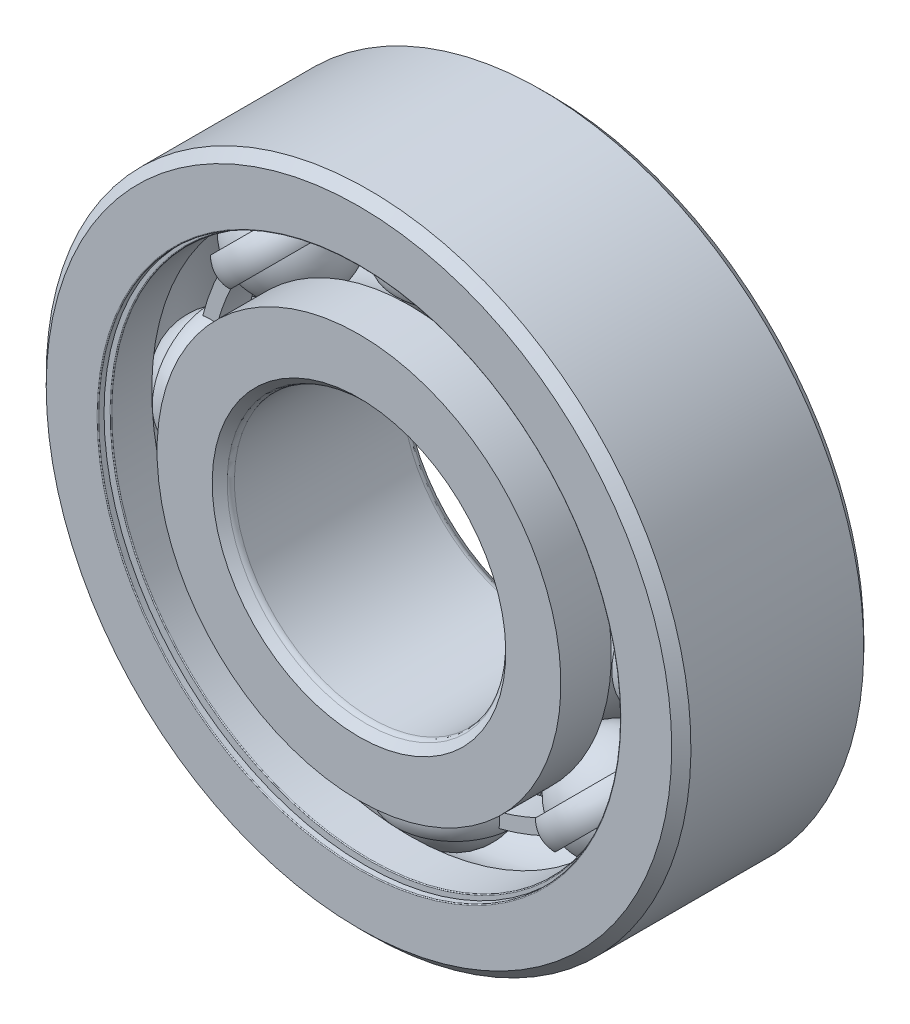
SolidWorks part; units mm, degrees
ref_plane "Front Plane" through (0, 0, 0) normal (0, 0, 1) x (1, 0, 0)
ref_plane "Top Plane" through (0, 0, 0) normal (0, 1, 0) x (1, 0, 0)
ref_plane "Right Plane" through (0, 0, 0) normal (1, 0, 0) x (0, 0, -1)
sketch "Sketch1" plane through (0, 0, 0) normal (0, 0, 1) x (1, 0, 0)
  line L0 (-23.5, 0) -> (23.5, 0) construction
  line L1 (-10, 0) -> (10, 0) construction
  circle A0 centre (0, 0) radius 10 construction
  circle A1 centre (0, 0) radius 23.5 construction
  point P3 (0, 0)
  point P6 (0, 0)
  point P7 (0, -10)
  point P11 (0, -23.5)
  point P12 (0, 10)
  point P13 (0, 23.5)
  dimension "OD" = 47
  dimension "ID" = 20
sketch "Sketch2" plane through (0, 0, 0) normal (1, 0, 0) x (0, 0, -1)
  line L0 (-7, 23.5) -> (7, 23.5) construction
  line L1 (0, 23.5) -> (0, -23.5) construction
  line L2 (6.3, 23.5) -> (-6.3, 23.5)
  line L3 (-6.3, 23.5) -> (-7, 22.8)
  line L4 (-7, 22.8) -> (-7, 18.7808)
  line L5 (-7, 18.7808) -> (-3.325, 18.7808)
  line L6 (7, 18.7808) -> (3.325, 18.7808)
  line L7 (7, 22.8) -> (7, 18.7808)
  line L8 (6.3, 23.5) -> (7, 22.8)
  line L9 (0, 23.5) -> (0, 16.75) construction
  line L10 (0, 16.75) -> (0, 10) construction
  line L11 (0, 23.5) -> (0, -23.5) construction
  line L12 (-7, 0) -> (7, 0) construction
  line L13 (7, 10) -> (-7, 10) construction
  line L14 (0, 20.6461) -> (0, 12.8539) construction
  line L15 (-7, -10) -> (7, -10) construction
  line L16 (-7, -10) -> (-7, 10) construction
  line L17 (7, 23.5) -> (7, -23.5) construction
  arc A0 (-3.325, 18.7808) -> (3.325, 18.7808) centre (0, 16.75) cw
  circle A1 centre (0, 16.75) radius 3.8961 construction
  point P14 (0, 10)
  point P17 (0, 0)
  point P21 (0, 23.5)
  point P29 (0, 10)
  point P30 (0, -10)
  point P35 (0, 20.6461)
  dimension "Approx. Ball Dia." = 7.7922
  dimension "Width" = 14
  dimension "D1" = 45
  dimension "D2" = 0.7
  dimension "D3" = 6.65
  dimension "D4" = 2.0308
  dimension "For Shaft Diameter" = 20
  dimension "For Housing ID" = 47
sketch "Sketch3" plane through (0, 0, 0) normal (1, 0, 0) x (0, 0, -1)
  line L0 (6.3, 23.5) -> (7, 22.8) construction
  line L1 (7, 22.8) -> (7, 18.7808) construction
  line L2 (7, 18.7808) -> (3.325, 18.7808) construction
  line L3 (-7, 18.7808) -> (-3.325, 18.7808) construction
  line L4 (-7, 22.8) -> (-7, 18.7808) construction
  line L5 (-6.3, 23.5) -> (-7, 22.8) construction
  line L6 (6.3, 23.5) -> (-6.3, 23.5) construction
  line L7 (6.3, 23.5) -> (7, 22.8)
  line L8 (7, 22.8) -> (7, 18.7808)
  line L9 (7, 18.7808) -> (3.325, 18.7808)
  line L10 (-7, 18.7808) -> (-3.325, 18.7808)
  line L11 (-7, 22.8) -> (-7, 18.7808)
  line L12 (-6.3, 23.5) -> (-7, 22.8)
  line L13 (6.3, 23.5) -> (-6.3, 23.5)
  arc A0 (3.325, 18.7808) -> (-3.325, 18.7808) centre (0, 16.75) ccw construction
  arc A1 (3.325, 18.7808) -> (-3.325, 18.7808) centre (0, 16.75) ccw
revolve "Revolve1" add sketch "Sketch3" angle 360 about L12
sketch "Sketch8" plane through (0, 0, 0) normal (1, 0, 0) x (0, 0, -1)
  line L0 (-7, 18.7808) -> (-3.325, 18.7808) construction
  line L1 (-6.552, 18.7808) -> (-6.3, 18.7808)
  line L2 (-6.552, 18.7808) -> (-6.552, 20.3538) construction
  line L3 (-6.552, 20.3538) -> (-6.3, 20.3538)
  line L4 (-6.3, 18.7808) -> (-6.3, 20.3538)
  line L5 (7, 18.7808) -> (3.325, 18.7808) construction
  line L6 (6.3, 18.7808) -> (6.552, 18.7808)
  line L7 (6.3, 18.7808) -> (6.3, 20.3538)
  line L8 (6.3, 20.3538) -> (6.552, 20.3538)
  line L9 (6.552, 18.7808) -> (6.552, 20.3538) construction
  line L10 (-6.3, 20.3538) -> (6.3, 20.3538) construction
  line L11 (0, 23.5) -> (0, -23.5) construction
  line L12 (-6.552, 20.3538) -> (-6.552, 21.9269) construction
  line L13 (-6.552, 21.9269) -> (-6.552, 23.5) construction
  line L14 (-7, 23.5) -> (7, 23.5) construction
  line L15 (-6.552, 18.7808) -> (-7, 18.7808)
  line L16 (-7, 18.7808) -> (-7, 19.0328)
  line L17 (-7, 22.8) -> (-7, 18.7808) construction
  line L18 (-7, 19.0328) -> (-6.552, 19.0328)
  line L19 (-6.552, 19.0328) -> (-6.552, 20.3538)
  line L20 (6.552, 18.7808) -> (7, 18.7808)
  line L21 (7, 18.7808) -> (7, 19.0328)
  line L22 (7, 22.8) -> (7, 18.7808) construction
  line L23 (7, 19.0328) -> (6.552, 19.0328)
  line L24 (6.552, 19.0328) -> (6.552, 20.3538)
  point P12 (0, 20.3538)
  dimension "D1" = 12.6
  dimension "D2" = 0.252
revolve "Cut-Revolve1" cut sketch "Sketch8" angle 360 about L12
sketch "Sketch4" plane through (0, 0, 0) normal (1, 0, 0) x (0, 0, -1)
  line L0 (0, 23.5) -> (0, -23.5) construction
  line L1 (0, 23.5) -> (0, -23.5) construction
  line L2 (-6.3, 10) -> (-7, 10.7)
  line L3 (-7, 10.7) -> (-7, 14.7192)
  line L5 (-7, 14.7192) -> (-3.325, 14.7192)
  line L6 (-6.3, 10) -> (6.3, 10)
  line L8 (6.3, 10) -> (7, 10.7)
  line L10 (7, 10.7) -> (7, 14.7192)
  line L11 (7, 14.7192) -> (3.325, 14.7192)
  line L12 (-7, 22.8) -> (-7, 18.7808) construction
  line L13 (6.3, 23.5) -> (7, 22.8) construction
  line L15 (7, -22.8) -> (7, 22.8) construction
  line L16 (6.3, 23.5) -> (6.3, -23.5) construction
  arc A1 (3.325, 14.7192) -> (-3.325, 14.7192) centre (0, 16.75) cw
  circle A2 centre (0, 16.75) radius 3.8961 construction
  point P1 (0, 10)
revolve "Revolve2" add sketch "Sketch4" angle 360 about L12
sketch "Sketch5" plane through (0, 0, 0) normal (1, 0, 0) x (0, 0, -1)
  line L0 (-3.8961, 16.75) -> (3.8961, 16.75)
  arc A2 (-3.8961, 16.75) -> (3.8961, 16.75) centre (0, 16.75) cw
  arc A3 (3.325, 18.7808) -> (-3.325, 18.7808) centre (0, 16.75) ccw construction
revolve "Revolve3" add sketch "Sketch5" angle 360 about L0
sketch "Sketch6" plane through (0, 0, 0) normal (1, 0, 0) x (0, 0, -1)
  line L0 (-3.325, 18.7808) -> (-3.325, 17.7654) construction
  line L1 (-3.325, 17.7654) -> (-3.325, 16.75) construction
  line L2 (-3.325, 16.75) -> (-3.325, 15.7346) construction
  line L3 (-3.325, 15.7346) -> (-3.325, 14.7192) construction
  line L4 (-7, 17.7654) -> (-6.4602, 17.7654) construction
  line L5 (-3.325, 17.7654) -> (-3.325, 15.7346) construction
  line L7 (-6.4602, 17.7654) -> (-5.9205, 17.7654) construction
  line L8 (-5.9205, 17.7654) -> (-5.3807, 17.7654) construction
  line L10 (0, 23.5) -> (0, -23.5) construction
  line L11 (0, 23.5) -> (0, -23.5) construction
  line L12 (-7, 18.7808) -> (-7, 17.7654) construction
  line L13 (-4.3012, 17.7654) -> (-3.7615, 17.7654) construction
  line L14 (-7, 22.8) -> (-7, -22.8) construction
  line L15 (-7, 17.7654) -> (-7, 16.75) construction
  line L16 (-7, 16.75) -> (-7, 15.7346) construction
  line L17 (-7, 15.7346) -> (-7, 14.7192) construction
  line L18 (-5.3807, 17.7654) -> (-4.841, 17.7654) construction
  line L19 (-4.841, 17.7654) -> (-4.3012, 17.7654) construction
  line L20 (-3.7615, 17.7654) -> (-4.3012, 17.7654)
  line L21 (-7, 15.7346) -> (-6.4602, 15.7346) construction
  line L22 (-6.4602, 15.7346) -> (-5.9205, 15.7346) construction
  line L23 (-5.9205, 15.7346) -> (-5.3807, 15.7346) construction
  line L24 (-5.3807, 15.7346) -> (-4.841, 15.7346) construction
  line L25 (-4.841, 15.7346) -> (-4.3012, 15.7346) construction
  line L26 (-4.3012, 15.7346) -> (-3.7615, 15.7346) construction
  line L27 (-3.7615, 15.7346) -> (-4.3012, 15.7346)
  line L28 (-4.841, 17.7654) -> (-4.841, 15.7346) construction
  line L30 (-4.5711, 17.7654) -> (-4.5711, 15.7346) construction
  circle A0 centre (0, 16.75) radius 3.8961 construction
  arc A2 (-4.3012, 15.7346) -> (-4.3012, 17.7654) centre (-2.526, 16.75) cw
  arc A3 (-3.7615, 17.7654) -> (-3.7615, 15.7346) centre (0, 16.75) ccw
revolve "Revolve4" add sketch "Sketch6" angle 360 about L11
sketch "Sketch7" plane through (0, 0, 0) normal (0, 0, 1) x (1, 0, 0)
  line L0 (-3.8961, 16.75) -> (3.8961, 16.75) construction
  line L1 (0, 12.8539) -> (0, 20.6461) construction
  line L2 (0, 0) -> (6.7455, 15.3317) construction
  line L8 (0, 23.5) -> (0, -23.5) construction
  line L9 (12.3486, 11.317) -> (13.0971, 12.0031)
  line L10 (0, 23.5) -> (0, -23.5) construction
  line L11 (0, 17.7654) -> (0, 16.75)
  arc A1 (12.3486, 11.317) -> (0, 16.75) centre (0, 0) ccw
  arc A2 (13.0971, 12.0031) -> (0, 17.7654) centre (0, 0) ccw
  dimension "D1" = 47.496
  dimension "D2" = 7.7922
extrude "Boss-Extrude1" add sketch "Sketch7" along normal mid plane 2.3333
pattern_circular "CirPattern1" count 8 over 360 about axis through (0, 0, 7) along (0, 0, -1) of bodies 104 134
pattern_circular "CirPattern2" count 8 over 360 about axis through (0, 0, 7) along (0, 0, -1) of "Revolve4", "Boss-Extrude1" reverse direction yes
fillet "Fillet1" radius 0.063 4 edges at (0, -18.7808, -6.3) (0, -19.0328, -7) (0, -18.7808, 6.3) (0, -19.0328, 7)
fillet "Fillet2" radius 0.525 2 edges at (0, -10, -6.3) (0, -10, 6.3)
ref_plane "Plane1" through (6.7455, 15.3317, 0) normal (0.4027, 0.9153, 0) x (0.9153, -0.4027, 0)
sketch "Sketch9" plane through (6.7455, 15.3317, 0) normal (0.4027, 0.9153, 0) x (0.9153, -0.4027, 0)
  line L0 (-3.1792, -1.1667) -> (-3.1792, -3.5)
  line L1 (-3.1792, -3.5) -> (-1.379, -3.5)
  line L2 (-1.379, -3.5) -> (0, -2.3429)
  line L3 (0, -2.3429) -> (1.379, -3.5)
  line L4 (1.379, -3.5) -> (3.1792, -3.5)
  line L5 (3.1792, -3.5) -> (3.1792, -1.1667)
  line L6 (3.1792, -1.1667) -> (-3.1792, -1.1667)
  line L7 (0, -1.1667) -> (0, 0) construction
  line L8 (-3.1792, -1.1667) -> (-3.1792, 0) construction
  dimension "D1" = 2.3333
  dimension "D2" = 1.1667
  dimension "D3" = 40
extrude "Boss-Extrude2" [suppressed] add sketch "Sketch9" along normal blind 3.4091 draft 15 and the other way blind 3.4091 draft 10 separate body draft outward yes other way draft outward yes
fillet "Fillet3" [suppressed] radius 0.7
mirror "Mirror1" [suppressed] about plane through (0, 0, 0) normal (0, 0, 1) of bodies 149
pattern_circular "CirPattern3" [suppressed] count 8 over 360 about axis through (0, 0, 7) along (0, 0, -1) of bodies 158 149
ref_axis "Axis1" through (0, 0, -7.7) along (0, 0, 1)
equation "\"D2@Sketch2\" = \"Width@Sketch2\" * .05"
equation "\"D3@Sketch2\"=\"Width@Sketch2\" * .475"
equation "\"D4@Sketch2\" =  (  (  ( \"OD@Sketch1\" - \"Width@Sketch2\" )  / 2 )  / 3.25 )  / 2.5"
equation "\"D1@Boss-Extrude1\" = \"Width@Sketch2\" / 6"
equation "\"D1@Sketch8\"=\"Width@Sketch2\"*.9"
equation "\"D2@Sketch8\"=\"D1@Sketch8\"*.02"
equation "\"D1@Fillet1\" = \"D2@Sketch8\" * .25"
equation "\"D1@Fillet2\" = \"D2@Sketch2\" * .75"
equation "\"Approx No of Balls\"= ( pi * \"OD@Sketch1\" ) * .4 / \"Approx. Ball Dia.@Sketch2\""
equation "\"D1@CirPattern1\"=\"Approx No of Balls\""
equation "\"D1@Sketch7\"=360/\"Approx No of Balls\""
equation "\"D1@CirPattern2\"=\"Approx No of Balls\""
equation "\"D2@Sketch7\"=\"Approx. Ball Dia.@Sketch2\""
equation "\"D2@Sketch9\"=\"d1@boss-extrude1\"*.5"
equation "\"D1@Sketch9\"=\"D2@Sketch9\"*2"
equation "\"D1@Boss-Extrude2\"=\"Approx. Ball Dia.@Sketch2\"*.4375"
equation "\"D2@Boss-Extrude2\"=\"D1@Boss-Extrude2\""
equation "\"D1@CirPattern3\"=\"Approx No of Balls\""
equation "\"D1@Fillet3\"=\"D1@Sketch9\" * .3"
